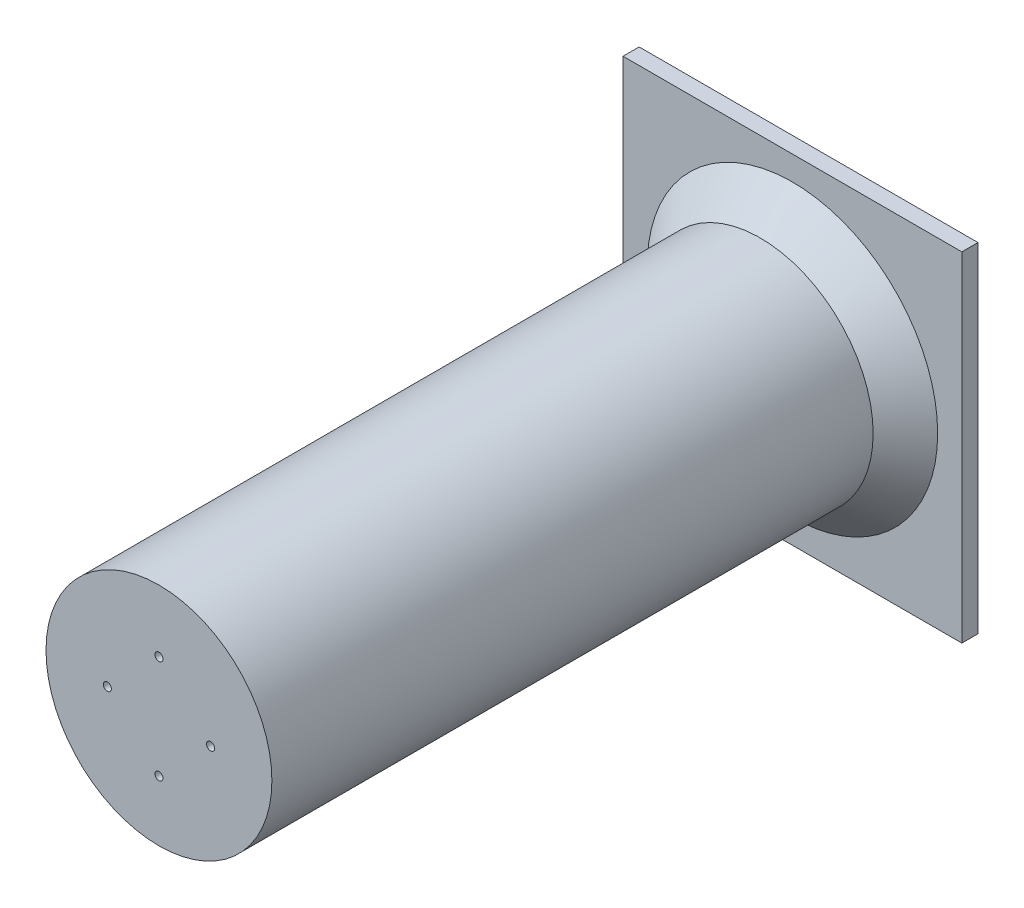
SolidWorks part; units mm, degrees
ref_plane "Alzado" through (0, 0, 0) normal (0, 0, 1) x (1, 0, 0)
ref_plane "Planta" through (0, 0, 0) normal (0, 1, 0) x (1, 0, 0)
ref_plane "Vista lateral" through (0, 0, 0) normal (1, 0, 0) x (0, 0, -1)
sketch "Croquis1" plane through (0, 0, 0) normal (0, 0, 1) x (1, 0, 0)
  line L1 (-117.2917, 97.7627) -> (131.4683, 97.7627)
  line L2 (-117.2917, 97.7627) -> (-117.2917, -97.2373)
  line L3 (-117.2917, -97.2373) -> (131.4683, -97.2373)
  line L4 (131.4683, 97.7627) -> (131.4683, -97.2373)
  dimension "D1" = 248.76
  dimension "D2" = 195
extrude "Saliente-Extruir1" add sketch "Croquis1" along normal blind 5
sketch "Croquis2" plane through (0, 0, 5) normal (0, 0, 1) x (1, 0, 0)
  line L0 (-117.2917, 0.2627) -> (131.4683, 0.2627) construction
  line L1 (-117.2917, 97.7627) -> (-117.2917, -97.2373) construction
  line L2 (131.4683, -97.2373) -> (131.4683, 97.7627) construction
  line L3 (-117.2917, -97.2373) -> (-69.2917, -97.2373)
  line L4 (-117.2917, -97.2373) -> (131.4683, -97.2373) construction
  line L5 (-69.2917, -97.2373) -> (-69.2917, -67.2373)
  line L6 (-69.2917, -67.2373) -> (-117.2917, -67.2373)
  line L7 (-117.2917, -67.2373) -> (-117.2917, -97.2373)
  line L8 (131.4683, 67.7627) -> (101.4683, 67.7627)
  line L9 (131.4683, -97.2373) -> (101.4683, -97.2373)
  line L10 (131.4683, -97.2373) -> (131.4683, -67.2373)
  line L11 (131.4683, -67.2373) -> (101.4683, -67.2373)
  line L12 (101.4683, -97.2373) -> (101.4683, -67.2373)
  line L13 (101.4683, 97.7627) -> (101.4683, 67.7627)
  line L14 (131.4683, 97.7627) -> (101.4683, 97.7627)
  line L15 (131.4683, 97.7627) -> (131.4683, 67.7627)
  line L16 (-69.2917, 67.7627) -> (-117.2917, 67.7627)
  line L17 (-69.2917, 97.7627) -> (-69.2917, 67.7627)
  line L18 (-117.2917, 97.7627) -> (-69.2917, 97.7627)
  line L19 (-117.2917, 67.7627) -> (-117.2917, 97.7627)
  dimension "D1" = 48
  dimension "D2" = 30
  dimension "D3" = 30
  dimension "D4" = 30
extrude "Cortar-Extruir1" cut sketch "Croquis2" against normal blind 2
sketch "Croquis3" plane through (0, 0, 5) normal (0, 0, 1) x (1, 0, 0)
  line L0 (-69.2917, 97.7627) -> (-117.2917, 97.7627) construction
  line L1 (116.4683, 83.7627) -> (116.4683, 67.7627) construction
  line L3 (116.4683, -83.2373) -> (116.4683, -67.2373) construction
  line L5 (131.4683, -67.2373) -> (101.4683, -67.2373) construction
  line L6 (101.4683, 67.7627) -> (131.4683, 67.7627) construction
  line L7 (-93.2917, 83.7627) -> (-93.2917, 67.7627) construction
  line L8 (-117.2917, 67.7627) -> (-69.2917, 67.7627) construction
  line L9 (-93.2917, -83.2373) -> (-93.2917, -67.2373) construction
  line L10 (-69.2917, -67.2373) -> (-117.2917, -67.2373) construction
  circle A0 centre (-93.2917, 83.7627) radius 2.375
  circle A1 centre (-93.2917, -83.2373) radius 2.375
  circle A2 centre (116.4683, 83.7627) radius 2.375
  circle A3 centre (116.4683, -83.2373) radius 2.375
  dimension "D2" = 4.75
  dimension "D3" = 4.75
  dimension "D5" = 4.75
  dimension "D6" = 4.75
  dimension "D1" = 14
  dimension "D4" = 14
  dimension "D7" = 209.76
  dimension "D8" = 16
  dimension "D9" = 16
extrude "Cortar-Extruir2" cut sketch "Croquis3" against normal blind 10
sketch "Croquis4" plane through (0, 0, 0) normal (0, 0, -1) x (-1, 0, 0)
  line L7 (-131.4683, 97.7627) -> (117.2917, 97.7627) construction
  line L9 (117.2917, 97.7627) -> (117.2917, -97.2373) construction
  circle A0 centre (13.4317, 0.2627) radius 35
  dimension "D3" = 70
  dimension "D1" = 103.86
  dimension "D2" = 97.5
extrude "Saliente-Extruir2" add sketch "Croquis4" along normal blind 196.5 contours A0
sketch "Croquis5" plane through (0, 0, 0) normal (0, 0, -1) x (-1, 0, 0)
  line L0 (-131.4683, 0.2627) -> (117.2917, 0.2627) construction
  line L1 (-131.4683, -97.2373) -> (-131.4683, 97.7627) construction
  line L2 (117.2917, 97.7627) -> (117.2917, -97.2373) construction
  circle A0 centre (-76.9683, 0.2627) radius 12.5
  dimension "D1" = 25
  dimension "D2" = 54.5
extrude "Cortar-Extruir3" cut sketch "Croquis5" against normal blind 10
sketch "Croquis6" plane through (0, 0, 0) normal (0, 0, -1) x (-1, 0, 0)
  line L0 (-131.4683, 97.7627) -> (117.2917, 97.7627) construction
  line L1 (-7.0883, 97.7627) -> (-7.0883, -97.2373)
  line L2 (117.2917, -97.2373) -> (-131.4683, -97.2373) construction
  line L3 (-7.0883, 97.7627) -> (117.2917, 97.7627)
  line L4 (117.2917, 97.7627) -> (117.2917, -97.2373)
  line L5 (117.2917, -97.2373) -> (-7.0883, -97.2373)
  line L6 (-131.4683, 0.2627) -> (56.0317, 0.2627)
  line L7 (-131.4683, -97.2373) -> (-131.4683, 97.7627) construction
  circle A1 centre (56.0317, 0.2627) radius 100
  dimension "D1" = 200
  dimension "D2" = 187.5
sketch "Croquis9" plane through (0, 97.7627, 0) normal (0, 1, 0) x (1, 0, 0)
  line L0 (7.0883, 0) -> (7.0883, -5)
  line L1 (131.4683, 0) -> (-117.2917, 0) construction
  line L2 (101.4683, -5) -> (-69.2917, -5) construction
ref_plane "Plano3" through (7.0883, 0, 0) normal (1, 0, 0) x (0, 0, -1)
sketch "Croquis12" plane through (7.0883, 0, 0) normal (1, 0, 0) x (0, 0, -1)
  line L0 (0, 97.7627) -> (0, 67.7627)
  line L1 (0, 67.7627) -> (12, 67.7627)
  line L2 (12, 67.7627) -> (12, 97.7627)
  line L3 (12, 97.7627) -> (0, 97.7627)
  line L4 (0, -97.2373) -> (12, -97.2373)
  line L5 (12, -97.2373) -> (12, -67.2373)
  line L6 (12, -67.2373) -> (0, -67.2373)
  line L7 (0, -67.2373) -> (0, -97.2373)
  dimension "D1" = 30
  dimension "D2" = 12
  dimension "D3" = 30
  dimension "D4" = 12
extrude "Saliente-Extruir3" add sketch "Croquis12" along normal mid plane 8
fillet "Redondeo1" radius 10 2 edges at (7.0883, -67.2373, 0) (7.0883, 67.7627, 0)
fillet "Redondeo2" radius 10 2 edges at (7.0883, 67.7627, -12) (7.0883, -67.2373, -12)
fillet "Redondeo3" radius 10 2 edges at (7.0883, -97.2373, -12) (7.0883, 97.7627, -12)
sketch "Croquis13" plane through (11.0883, 0, 0) normal (1, 0, 0) x (0, 0, -1)
  line L0 (-5, 0.2627) -> (196.5, 0.2627) construction
  line L1 (-5, -67.2373) -> (-5, 67.7627) construction
  line L2 (196.5, -34.7373) -> (196.5, 35.2627) construction
  line L3 (6, 87.7627) -> (12, 87.7627) construction
  line L4 (6, 87.7627) -> (6, 77.7627) construction
  circle A0 centre (6, 87.7627) radius 1.625
  circle A1 centre (6, 77.7627) radius 1.625
  circle A2 centre (6, -77.2373) radius 1.625
  circle A3 centre (6, -87.2373) radius 1.625
  dimension "D3" = 3.25
  dimension "D4" = 3.25
  dimension "D1" = 6
extrude "Cortar-Extruir5" cut sketch "Croquis13" against normal through all both and the other way through all
sketch "Croquis14" plane through (0, 0, 0) normal (0, 0, -1) x (-1, 0, 0)
  line L0 (-7.0883, 97.7627) -> (-7.0883, -97.2373)
  line L1 (-7.0883, 97.7627) -> (117.2917, 97.7627)
  line L2 (117.2917, 97.7627) -> (117.2917, -97.2373)
  line L3 (117.2917, -97.2373) -> (-7.0883, -97.2373)
sketch "Croquis15" plane through (0, 0, 5) normal (0, 0, 1) x (1, 0, 0)
  line L0 (111.4683, 67.7627) -> (131.4683, 67.7627)
  line L1 (111.4683, 67.7627) -> (111.4683, 60.0127)
  line L2 (131.4683, -67.2373) -> (101.4683, -67.2373) construction
  line L3 (111.4683, -67.2373) -> (111.4683, -59.4873)
  line L4 (111.4683, -59.4873) -> (125.2183, -59.4873)
  line L5 (125.2183, -59.4873) -> (125.2183, 60.0127)
  line L6 (111.4683, 60.0127) -> (125.2183, 60.0127)
  line L7 (111.4683, -67.2373) -> (131.4683, -67.2373)
  line L10 (131.4683, -67.2373) -> (131.4683, 67.7627)
  dimension "D1" = 119.5
  dimension "D2" = 7.75
  dimension "D3" = 13.75
extrude "Cortar-Extruir7" cut sketch "Croquis15" against normal blind 2
sketch "Croquis16" plane through (0, 0, -196.5) normal (0, 0, -1) x (-1, 0, 0)
  line L1 (-39.0683, -52.2373) -> (65.9317, -52.2373)
  line L2 (-39.0683, -52.2373) -> (-39.0683, 52.7627)
  line L3 (-39.0683, 52.7627) -> (65.9317, 52.7627)
  line L4 (65.9317, -52.2373) -> (65.9317, 52.7627)
  line L5 (-39.0683, -52.2373) -> (65.9317, 52.7627) construction
  line L6 (-39.0683, 52.7627) -> (65.9317, -52.2373) construction
  point P0 (13.4317, 0.2627)
  dimension "D1" = 105
  dimension "D2" = 105
extrude "Saliente-Extruir4" add sketch "Croquis16" along normal blind 5
fillet "Chaflán1" radius 10 1 edges at (-48.4317, 0.2627, -196.5) type face fillet profile chamfer first side face at (-48.4317, 0.2627, -196.5) second side face at (-48.4317, 0.2627, -196.5)
sketch "Croquis17" plane through (0, 0, 5) normal (0, 0, 1) x (1, 0, 0)
  circle A0 centre (-13.4317, 0) radius 35
  dimension "D2" = 70
sketch "Croquis18" plane through (0, 0, 5) normal (0, 0, 1) x (1, 0, 0)
  line L0 (-13.4317, 0) -> (-13.4317, 16) construction
  circle A0 centre (-13.4317, 16) radius 1.625
  circle A1 centre (2.5683, 0) radius 1.625
  circle A2 centre (-13.4317, -16) radius 1.625
  circle A3 centre (-29.4317, 0) radius 1.625
  dimension "D2" = 3.25
  dimension "D1" = 16
  dimension "D3" = 4
extrude "Cortar-Extruir8" cut sketch "Croquis18" against normal blind 5
ref_plane "Plano4" through (-65.9317, -52.2373, -201.5) normal (0, 1, 0) x (1, 0, 0)
sketch "Croquis20" plane through (-65.9317, -52.2373, -201.5) normal (0, 1, 0) x (1, 0, 0)
  line L0 (197.4, -211.6862) -> (-51.36, -211.6862)
  line L1 (197.4, -211.6862) -> (197.4, -201.3138)
  line L2 (-51.36, -211.6862) -> (-51.36, -201.3138)
  line L3 (197.4, -201.3138) -> (-51.36, -201.3138)
  line L4 (197.4, -211.6862) -> (-51.36, -201.3138) construction
  line L5 (-51.36, -211.6862) -> (197.4, -201.3138) construction
  point P1 (73.02, -206.5)
extrude "Cortar-Extruir13" cut sketch "Croquis20" against normal through all both and the other way through all
sketch "Croquis21" plane through (11.0883, 0, 0) normal (1, 0, 0) x (0, 0, -1)
  line L1 (0.1862, -97.2373) -> (75.1913, -97.2373)
  line L2 (0.1862, -97.2373) -> (0.1862, -54.6828)
  line L3 (0.1862, -54.6828) -> (75.1913, -54.6828)
  line L4 (75.1913, -97.2373) -> (75.1913, -54.6828)
  line L5 (0.1862, 97.7627) -> (80.8734, 97.7627)
  line L6 (0.1862, 97.7627) -> (0.1862, 53.0074)
  line L7 (0.1862, 53.0074) -> (80.8734, 53.0074)
  line L8 (80.8734, 97.7627) -> (80.8734, 53.0074)
extrude "Cortar-Extruir14" cut sketch "Croquis21" against normal through all both and the other way through all
sketch "Croquis22" plane through (0, 0, -0.1862) normal (0, 0, 1) x (1, 0, 0)
  circle A0 centre (-29.4317, 0) radius 1.25
  circle A1 centre (-13.4317, 16) radius 1.25
  circle A2 centre (2.5683, 0) radius 1.25
  circle A3 centre (-13.4317, -16) radius 1.25
  dimension "D1" = 2.5
  dimension "D2" = 4
extrude "Cortar-Extruir15" cut sketch "Croquis22" against normal blind 15 and the other way through all
